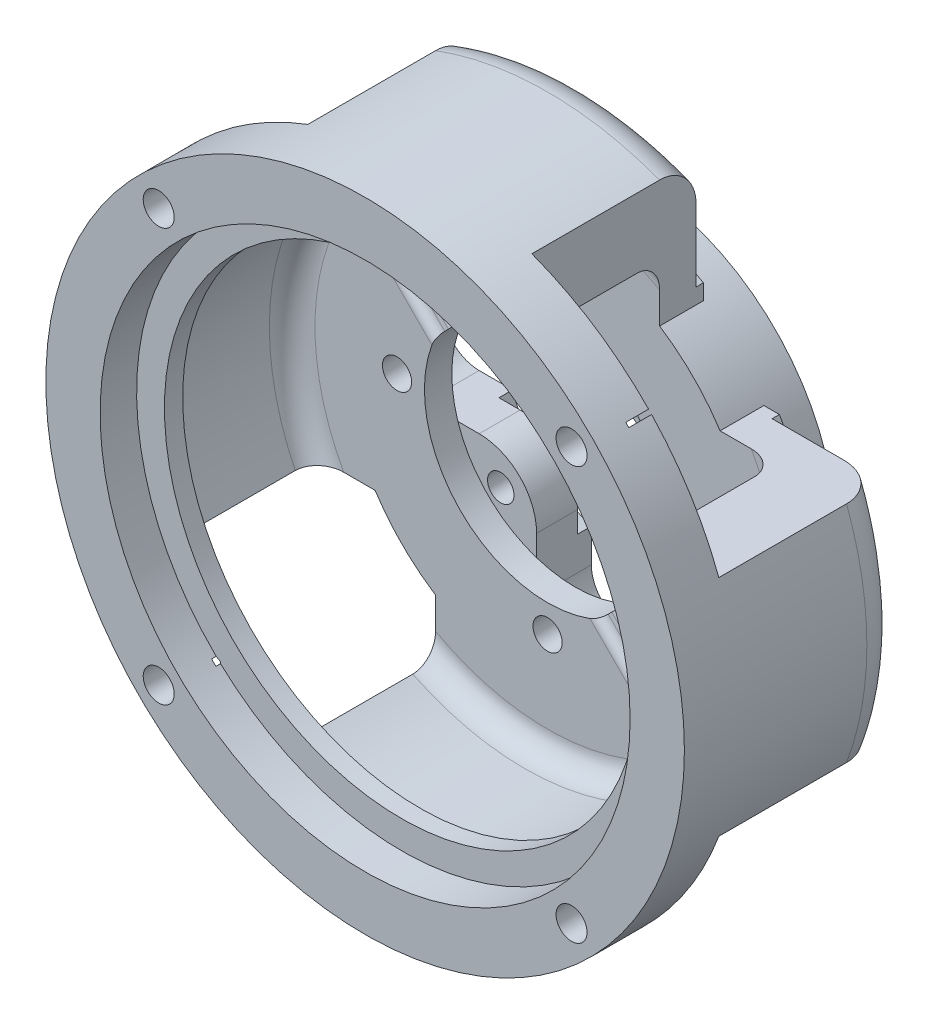
SolidWorks part; units mm, degrees
ref_plane "前视基准面" through (0, 0, 0) normal (0, 0, 1) x (1, 0, 0)
ref_plane "上视基准面" through (0, 0, 0) normal (0, 1, 0) x (1, 0, 0)
ref_plane "右视基准面" through (0, 0, 0) normal (1, 0, 0) x (0, 0, -1)
sketch "草图1" plane through (0, 0, 0) normal (0, 1, 0) x (1, 0, 0)
  line L0 (35, 30.0102) -> (0, 30.0102)
  line L1 (0, 30.0102) -> (0, 24.0102)
  line L2 (0, 24.0102) -> (35, 24.0102)
  line L3 (35, 24.0102) -> (35, 30.0102)
  line L4 (0, 30.0102) -> (0, 24.0102) construction
revolve "旋转1" add sketch "草图1" angle 360 about L4
sketch "草图2" plane through (0, 0, -30.0102) normal (0, 0, -1) x (-1, 0, 0)
  line L24 (-21.0253, -19.8524) -> (-24.2296, -19.8524)
  line L25 (-24.2296, -19.8524) -> (-25.8317, -22.6274)
  line L26 (-19.4231, -22.6274) -> (-21.0253, -19.8524)
  line L27 (-21.0253, -25.4024) -> (-19.4231, -22.6274)
  line L28 (-24.2296, -25.4024) -> (-21.0253, -25.4024)
  line L29 (-25.8317, -22.6274) -> (-24.2296, -25.4024)
  line L75 (-19.4231, -22.6274) -> (-25.8317, -22.6274) construction
  line L76 (-21.0253, -19.8524) -> (-24.2296, -25.4024) construction
  line L77 (-24.2296, -19.8524) -> (-21.0253, -25.4024) construction
  line L78 (0, 0) -> (-22.6274, -22.6274) construction
  line L169 (0, 0) -> (0, -46.6036) construction
  line L170 (-22.6274, 25.8317) -> (-25.4024, 24.2296)
  line L171 (-19.8524, 24.2296) -> (-22.6274, 25.8317)
  line L172 (-19.8524, 21.0253) -> (-19.8524, 24.2296)
  line L173 (-22.6274, 19.4231) -> (-19.8524, 21.0253)
  line L174 (-25.4024, 21.0253) -> (-22.6274, 19.4231)
  line L175 (-25.4024, 24.2296) -> (-25.4024, 21.0253)
  line L176 (25.8317, 22.6274) -> (24.2296, 25.4024)
  line L177 (24.2296, 19.8524) -> (25.8317, 22.6274)
  line L178 (21.0253, 19.8524) -> (24.2296, 19.8524)
  line L179 (19.4231, 22.6274) -> (21.0253, 19.8524)
  line L180 (21.0253, 25.4024) -> (19.4231, 22.6274)
  line L181 (24.2296, 25.4024) -> (21.0253, 25.4024)
  line L182 (22.6274, -25.8317) -> (25.4024, -24.2296)
  line L183 (19.8524, -24.2296) -> (22.6274, -25.8317)
  line L184 (19.8524, -21.0253) -> (19.8524, -24.2296)
  line L185 (22.6274, -19.4231) -> (19.8524, -21.0253)
  line L186 (25.4024, -21.0253) -> (22.6274, -19.4231)
  line L187 (25.4024, -24.2296) -> (25.4024, -21.0253)
  point P24 (0, 0)
  point P41 (0, 0)
  point P74 (0, 0)
  point P165 (0, 0)
  dimension "D1" = 4
  dimension "D2" = 45
extrude "切除-拉伸1" cut sketch "草图2" against normal blind 2.5
hole_wizard "M48 六角头螺栓的柱形沉头孔1" positions "草图15" profile "草图14" counterbore size "M48" standard "ANSI Metric" end condition through all
sketch "草图15" plane through (0, 0, -24.0102) normal (0, 0, 1) x (1, 0, 0)
  point P0 (0, 0)
sketch "草图14" plane through (0, 0, -24.0102) normal (1, 0, 0) x (0, -1, 0)
  line L0 (0, 0) -> (0, 6)
  line L1 (0, 6) -> (26, 6)
  line L3 (26, 6) -> (26, 4)
  line L4 (26, 4) -> (29.05, 4)
  line L5 (29.05, 4) -> (29.05, 0)
  line L7 (29.05, 0) -> (0, 0)
  line L11 (0, -6.35) -> (0, 107.95) construction
  dimension "通孔孔直径" = 52
  dimension "通孔孔深度" = 6
  dimension "柱形沉头孔直径" = 58.1
  dimension "柱形沉头孔深度" = 4
sketch "草图17" plane through (0, 0, -30.0102) normal (0, 0, -1) x (-1, 0, 0)
  line L0 (0, 0) -> (-22.6274, -22.6274) construction
  line L1 (0, 0) -> (0, -49.8277) construction
  circle A0 centre (-22.6274, -22.6274) radius 1.7
  circle A16 centre (-22.6274, 22.6274) radius 1.7
  circle A17 centre (22.6274, 22.6274) radius 1.7
  circle A18 centre (22.6274, -22.6274) radius 1.7
  point P13 (0, 0)
  point P16 (0, 0)
  point P27 (0, 0)
  dimension "D2" = 45
  dimension "D1" = 4
extrude "切除-拉伸2" cut sketch "草图17" against normal through all both and the other way through all
sketch "草图18" plane through (0, 0, -30.0102) normal (0, 0, -1) x (-1, 0, 0)
  circle A1 centre (0, 0) radius 35
extrude "凸台-拉伸1" add sketch "草图18" along normal blind 23
sketch "草图19" plane through (0, 0, -30.0102) normal (0, 0, 1) x (1, 0, 0)
  circle A0 centre (0, 0) radius 28
  dimension "D1" = 56
extrude "切除-拉伸3" cut sketch "草图19" against normal blind 14
sketch "草图20" plane through (0, 0, -53.0102) normal (0, 0, -1) x (-1, 0, 0)
  line L0 (0, 0) -> (0, -35) construction
  line L1 (0, 0) -> (-19.0624, -29.3535) construction
  line L2 (0, 0) -> (-29.3535, -19.0624) construction
  line L13 (-18.912, -12.2816) -> (-32.7744, -12.2816)
  line L14 (-12.2816, -32.7744) -> (-12.2816, -18.912) construction
  line L15 (-18.912, -12.2816) -> (-32.7744, -12.2816) construction
  line L16 (-12.2816, 18.912) -> (-12.2816, 32.7744)
  line L17 (-12.2816, -18.912) -> (-12.2816, -32.7744)
  line L18 (-18.912, 12.2816) -> (-32.7744, 12.2816)
  line L19 (18.912, 12.2816) -> (32.7744, 12.2816)
  line L20 (12.2816, 18.912) -> (12.2816, 32.7744)
  line L21 (12.2816, -18.912) -> (12.2816, -32.7744)
  line L22 (18.912, -12.2816) -> (32.7744, -12.2816)
  circle A0 centre (0, 0) radius 35 construction
  arc A1 (-18.912, -12.2816) -> (-12.2816, -18.912) centre (0, 0) ccw
  arc A2 (-29.3535, -19.0624) -> (-19.0624, -29.3535) centre (0, 0) ccw
  arc A19 (-12.2816, 18.912) -> (-18.912, 12.2816) centre (0, 0) ccw
  arc A20 (-19.0624, 29.3535) -> (-29.3535, 19.0624) centre (0, 0) ccw
  arc A21 (18.912, 12.2816) -> (12.2816, 18.912) centre (0, 0) ccw
  arc A22 (29.3535, 19.0624) -> (19.0624, 29.3535) centre (0, 0) ccw
  arc A23 (12.2816, -18.912) -> (18.912, -12.2816) centre (0, 0) ccw
  arc A24 (19.0624, -29.3535) -> (29.3535, -19.0624) centre (0, 0) ccw
  circle A25 centre (0, 0) radius 13.5
  dimension "D1" = 4
  dimension "D2" = 57
  dimension "D3" = 33
extrude "切除-拉伸5" cut sketch "草图20" against normal blind 23
sketch "草图21" plane through (0, 0, -53.0102) normal (0, 0, -1) x (-1, 0, 0)
  line L0 (0, 20.5051) -> (0, -20.6353) construction
  line L1 (-24.3457, 0) -> (20.7655, 0) construction
  line L2 (-4.2, 16.5) -> (-4.2, 10.5)
  line L3 (-10.5, 4.2) -> (-16.5, 4.2)
  line L4 (-20.5, 0.2) -> (-20.5, -0.2)
  line L5 (-16.5, -4.2) -> (-10.5, -4.2)
  line L6 (-4.2, -10.5) -> (-4.2, -16.5)
  line L7 (-0.2, -20.5) -> (0.2, -20.5)
  line L8 (4.2, -16.5) -> (4.2, -10.5)
  line L9 (10.5, -4.2) -> (16.5, -4.2)
  line L10 (20.5, -0.2) -> (20.5, 0.2)
  line L11 (16.5, 4.2) -> (10.5, 4.2)
  line L12 (4.2, 10.5) -> (4.2, 16.5)
  line L13 (0.2, 20.5) -> (-0.2, 20.5)
  arc A0 (-0.2, -20.5) -> (-4.2, -16.5) centre (-0.2, -16.5) cw
  arc A1 (0.2, -20.5) -> (4.2, -16.5) centre (0.2, -16.5) ccw
  arc A2 (20.5, -0.2) -> (16.5, -4.2) centre (16.5, -0.2) cw
  arc A3 (20.5, 0.2) -> (16.5, 4.2) centre (16.5, 0.2) ccw
  arc A4 (4.2, 16.5) -> (0.2, 20.5) centre (0.2, 16.5) ccw
  arc A5 (-0.2, 20.5) -> (-4.2, 16.5) centre (-0.2, 16.5) ccw
  arc A6 (-20.5, -0.2) -> (-16.5, -4.2) centre (-16.5, -0.2) ccw
  arc A7 (-20.5, 0.2) -> (-16.5, 4.2) centre (-16.5, 0.2) cw
  arc A8 (-10.5, 4.2) -> (-4.2, 10.5) centre (-10.5, 10.5) ccw
  arc A9 (4.2, 10.5) -> (10.5, 4.2) centre (10.5, 10.5) ccw
  arc A10 (10.5, -4.2) -> (4.2, -10.5) centre (10.5, -10.5) ccw
  arc A11 (-4.2, -10.5) -> (-10.5, -4.2) centre (-10.5, -10.5) ccw
  point P35 (-4.2, 4.2)
  dimension "D13" = 4
  dimension "D14" = 6.3
  dimension "D1" = 4.2
  dimension "D2" = 20.5
  dimension "D3" = 4.2
  dimension "D4" = 4.2
  dimension "D5" = 4.2
  dimension "D6" = 20.5
  dimension "D7" = 4.2
  dimension "D8" = 4.2
  dimension "D9" = 4.2
  dimension "D10" = 4.2
  dimension "D11" = 20.5
  dimension "D12" = 20.5
extrude "切除-拉伸6" cut sketch "草图21" against normal blind 6
sketch "草图22" plane through (0, 0, -47.0102) normal (0, 0, -1) x (-1, 0, 0)
  line L0 (0, 0) -> (-16.5, 0) construction
  line L1 (0, 0) -> (0, 16.5) construction
  line L2 (0, 0) -> (16.5, 0) construction
  line L3 (0, 0) -> (0, -16.5) construction
  circle A0 centre (-16.5, 0) radius 1.6
  circle A1 centre (0, 16.5) radius 1.6
  circle A2 centre (16.5, 0) radius 1.6
  circle A3 centre (0, -16.5) radius 1.6
  point P9 (0, 0)
  point P17 (0, 0)
extrude "切除-拉伸7" cut sketch "草图22" against normal blind 3
sketch "草图24" plane through (0, 0, -47.0102) normal (0, 0, -1) x (-1, 0, 0)
  line L0 (-12.83, -4.2) -> (-10.5, -4.2)
  line L1 (-4.2, -10.5) -> (-4.2, -12.83)
  line L2 (-12.83, 4.2) -> (-10.5, 4.2)
  line L3 (-4.2, 10.5) -> (-4.2, 12.83)
  line L4 (4.2, 12.83) -> (4.2, 10.5)
  line L5 (10.5, 4.2) -> (12.83, 4.2)
  line L6 (12.83, -4.2) -> (10.5, -4.2)
  line L7 (4.2, -10.5) -> (4.2, -12.83)
  line L8 (0, 0) -> (-8.1317, -8.1317) construction
  circle A0 centre (0, 0) radius 13.5
  arc A1 (4.2, -10.5) -> (10.5, -4.2) centre (10.5, -10.5) cw
  arc A2 (10.5, 4.2) -> (4.2, 10.5) centre (10.5, 10.5) cw
  arc A3 (-4.2, 10.5) -> (-10.5, 4.2) centre (-10.5, 10.5) cw
  arc A4 (-4.2, -10.5) -> (-10.5, -4.2) centre (-10.5, -10.5) ccw
  circle A6 centre (-8.1317, -8.1317) radius 1.45
  circle A7 centre (-8.1317, 8.1317) radius 1.45
  circle A8 centre (8.1317, 8.1317) radius 1.45
  circle A9 centre (8.1317, -8.1317) radius 1.45
  point P33 (-4.2, 4.2)
  point P47 (0, 0)
  dimension "D1" = 6.3
extrude "凸台-拉伸2" add sketch "草图24" along normal blind 4.5
sketch "草图25" plane through (0, 0, -53.0102) normal (0, 0, -1) x (-1, 0, 0)
  circle A0 centre (0, 0) radius 24
  circle A1 centre (0, 0) radius 35
extrude "切除-拉伸8" cut sketch "草图25" against normal blind 5
sketch "草图27" plane through (0, 0, -53.0102) normal (0, 0, -1) x (-1, 0, 0)
  circle A0 centre (0, 0) radius 24
  circle A1 centre (0, 0) radius 22.55
extrude "切除-拉伸9" cut sketch "草图27" against normal blind 4.2
sketch "草图29" plane through (0, 0, -53.0102) normal (0, 0, -1) x (-1, 0, 0)
  line L1 (-9.5, 11.5) -> (9.5, 11.5)
  line L2 (-11.5, 9.5) -> (-11.5, -9.5)
  line L3 (-9.5, -11.5) -> (9.5, -11.5)
  line L4 (11.5, 9.5) -> (11.5, -9.5)
  line L5 (-11.5, 11.5) -> (11.5, -11.5) construction
  line L6 (-11.5, -11.5) -> (11.5, 11.5) construction
  arc A0 (11.5, -9.5) -> (9.5, -11.5) centre (9.5, -9.5) cw
  arc A1 (-9.5, -11.5) -> (-11.5, -9.5) centre (-9.5, -9.5) cw
  arc A2 (11.5, 9.5) -> (9.5, 11.5) centre (9.5, 9.5) ccw
  arc A3 (-9.5, 11.5) -> (-11.5, 9.5) centre (-9.5, 9.5) ccw
  point P0 (0, 0)
  dimension "D1" = 2
extrude "切除-拉伸10" cut sketch "草图29" against normal blind 1.5
fillet "圆角1" radius 4 4 edges at (0, -35, -48.0102) (35, 0, -48.0102) (-35, 0, -48.0102) (0, 35, -48.0102)
fillet "圆角2" radius 2.5 4 edges at (28, 0, -44.0102) (0, -28, -44.0102) (-28, 0, -44.0102) (0, 28, -44.0102)
sketch "草图30" plane through (0, 0, -53.0102) normal (0, 0, -1) x (-1, 0, 0)
  line L0 (0, 0) -> (32.3138, -32.3138) construction
ref_plane "基准面1" through (0, 0, 0) normal (0.7071, -0.7071, 0) x (-0.7071, -0.7071, 0)
sketch "草图31" plane through (0, 0, 0) normal (0.7071, -0.7071, 0) x (-0.7071, -0.7071, 0)
  line L0 (4.6884, 44.0102) -> (4.6884, 48.8102) construction
  line L1 (-4.6884, 44.0102) -> (4.6884, 44.0102)
  line L2 (-4.6884, 44.0102) -> (-4.6884, 46.4102)
  line L3 (-4.6884, 46.4102) -> (4.6884, 46.4102)
  line L4 (4.6884, 44.0102) -> (4.6884, 46.4102)
extrude "切除-拉伸11" cut sketch "草图31" against normal through all both and the other way through all
fillet "圆角3" radius 1 8 edges at (15.5895, -8.9591, -44.0102) (15.5895, -8.9591, -46.4102) (8.9591, -15.5895, -44.0102) (8.9591, -15.5895, -46.4102) (-15.5895, 8.9591, -46.4102) (-8.9591, 15.5895, -44.0102) (-8.9591, 15.5895, -46.4102) (-15.5895, 8.9591, -44.0102)
